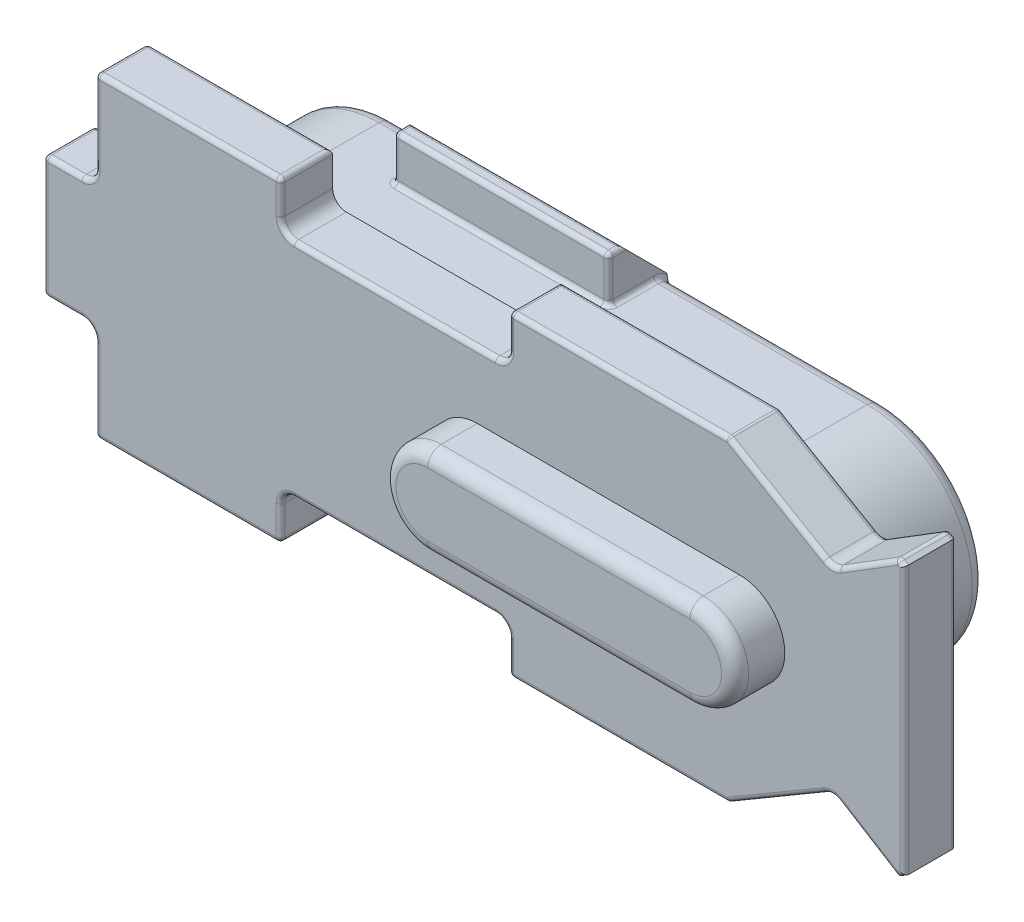
SolidWorks part; units mm, degrees
ref_plane "Front Plane" through (0, 0, 0) normal (0, 0, 1) x (1, 0, 0)
ref_plane "Top Plane" through (0, 0, 0) normal (0, 1, 0) x (1, 0, 0)
ref_plane "Right Plane" through (0, 0, 0) normal (1, 0, 0) x (0, 0, -1)
sketch "Sketch1" plane through (0, 0, 0) normal (0, 0, 1) x (1, 0, 0)
  line L0 (0, -8.89) -> (57.15, -8.89) construction
  line L1 (0, -12.319) -> (0, -5.461)
  line L2 (0, -5.461) -> (2.921, -5.461)
  line L3 (2.921, -5.461) -> (2.921, 0)
  line L4 (2.921, 0) -> (13.335, 0)
  line L5 (13.335, 0) -> (13.335, -2.667)
  line L6 (13.335, -2.667) -> (26.162, -2.667)
  line L7 (26.162, -2.667) -> (26.162, 0)
  line L8 (26.162, 0) -> (38.481, 0)
  line L9 (38.481, 0) -> (44.323, -3.429)
  line L10 (44.323, -3.429) -> (48.006, -1.143)
  line L11 (48.006, -1.143) -> (48.3742, -1.3591)
  line L12 (48.3742, -1.3591) -> (48.3742, -16.4209)
  line L13 (48.006, -16.637) -> (48.3742, -16.4209)
  line L18 (44.323, -14.351) -> (48.006, -16.637)
  line L19 (38.481, -17.78) -> (44.323, -14.351)
  line L20 (26.162, -17.78) -> (38.481, -17.78)
  line L21 (26.162, -15.113) -> (26.162, -17.78)
  line L22 (13.335, -15.113) -> (26.162, -15.113)
  line L23 (13.335, -17.78) -> (13.335, -15.113)
  line L24 (2.921, -17.78) -> (13.335, -17.78)
  line L25 (2.921, -12.319) -> (2.921, -17.78)
  line L26 (0, -12.319) -> (2.921, -12.319)
  point P16 (48.3742, -8.89)
  dimension "D2" = 17.78
  dimension "D3" = 6.858
  dimension "D4" = 2.921
  dimension "D5" = 10.414
  dimension "D6" = 12.827
  dimension "D7" = 2.667
  dimension "D9" = 35.56
  dimension "D10" = 10.922
  dimension "D11" = 41.402
  dimension "D12" = 45.085
  dimension "D13" = 15.494
extrude "Boss-Extrude1" add sketch "Sketch1" against normal blind 2.921
sketch "Sketch2" plane through (0, 0, 0) normal (0, 0, 1) x (1, 0, 0)
  line L0 (0, -8.89) -> (57.15, -8.89) construction
  line L1 (0, -5.461) -> (0, -12.319) construction
  line L3 (39.116, -8.89) -> (24.384, -8.89) construction
  line L4 (39.116, -11.43) -> (24.384, -11.43)
  line L5 (39.116, -6.35) -> (24.384, -6.35)
  arc A0 (39.116, -11.43) -> (39.116, -6.35) centre (39.116, -8.89) ccw
  arc A1 (24.384, -6.35) -> (24.384, -11.43) centre (24.384, -8.89) ccw
  point P8 (31.75, -8.89)
  point P13 (21.844, -8.89)
  point P14 (41.656, -8.89)
  point P15 (0, 0)
  dimension "D1" = 19.812
  dimension "D2" = 5.08
  dimension "D3" = 21.844
extrude "Boss-Extrude2" add sketch "Sketch2" along normal blind 2.794
sketch "Sketch3" plane through (0, 0, -2.921) normal (0, 0, -1) x (-1, 0, 0)
  line L0 (-57.15, -8.89) -> (0, -8.89) construction
  line L2 (0, -5.461) -> (0, -12.319) construction
  line L3 (-37.7825, -8.89) -> (-10.3505, -8.89) construction
  line L4 (-37.7825, -2.9845) -> (-10.3505, -2.9845)
  line L5 (-37.7825, -14.7955) -> (-10.3505, -14.7955)
  arc A0 (-37.7825, -2.9845) -> (-37.7825, -14.7955) centre (-37.7825, -8.89) ccw
  arc A1 (-10.3505, -14.7955) -> (-10.3505, -2.9845) centre (-10.3505, -8.89) ccw
  point P8 (-24.0665, -8.89)
  point P13 (-4.445, -8.89)
  point P14 (-43.688, -8.89)
  point P15 (0, 0)
  dimension "D1" = 39.243
  dimension "D2" = 11.811
  dimension "D3" = 4.445
extrude "Boss-Extrude3" add sketch "Sketch3" along normal blind 6.35
sketch "Sketch4" plane through (0, 0, -9.271) normal (0, 0, -1) x (-1, 0, 0)
  line L0 (-43.688, -8.89) -> (-4.445, -8.89) construction
  line L1 (-10.3505, -2.9845) -> (-37.7825, -2.9845) construction
  line L2 (-25.781, -2.9845) -> (-13.716, -2.9845)
  line L3 (-25.781, -2.9845) -> (-25.781, -0.4445)
  line L4 (-25.781, -0.4445) -> (-13.716, -0.4445)
  line L5 (-13.716, -2.9845) -> (-13.716, -0.4445)
  line L7 (-19.7485, -0.4445) -> (-19.7485, -2.9845) construction
  line L11 (-26.162, 0) -> (-26.162, -2.667) construction
  line L12 (-13.335, -2.667) -> (-13.335, 0) construction
  line L13 (-19.7485, -17.3355) -> (-19.7485, -14.7955) construction
  line L14 (-13.716, -14.7955) -> (-13.716, -17.3355)
  line L15 (-25.781, -17.3355) -> (-13.716, -17.3355)
  line L16 (-25.781, -14.7955) -> (-25.781, -17.3355)
  line L17 (-25.781, -14.7955) -> (-13.716, -14.7955)
  arc A0 (-37.7825, -2.9845) -> (-37.7825, -14.7955) centre (-37.7825, -8.89) ccw construction
  arc A1 (-10.3505, -14.7955) -> (-10.3505, -2.9845) centre (-10.3505, -8.89) ccw construction
  dimension "D1" = 12.065
  dimension "D2" = 2.54
extrude "Boss-Extrude4" add sketch "Sketch4" against normal blind 3.302
sketch "Sketch5" plane through (13.716, 0, 0) normal (-1, 0, 0) x (0, 0, 1)
  line L0 (-9.271, -8.89) -> (0, -8.89) construction
  line L1 (-9.271, -2.9845) -> (-9.271, -14.7955) construction
  line L2 (0, -5.461) -> (0, -12.319) construction
  line L3 (-9.271, -2.9845) -> (-6.731, -0.4445)
  line L5 (-6.731, -0.4445) -> (-9.271, -0.4445)
  line L6 (-9.271, -0.4445) -> (-9.271, -2.9845)
  line L7 (-5.969, -0.4445) -> (-9.271, -0.4445) construction
  line L8 (-9.271, -17.3355) -> (-9.271, -14.7955)
  line L9 (-6.731, -17.3355) -> (-9.271, -17.3355)
  line L10 (-9.271, -14.7955) -> (-6.731, -17.3355)
  dimension "D1" = 45
extrude "Cut-Extrude2" cut sketch "Sketch5" against normal through all
fillet "Fillet1" radius 0.762 18 edges at (12.0333, -14.7955, -9.271) (4.445, -8.89, -9.271) (12.0332, -2.9845, -9.271) (31.7817, -2.9845, -9.271) (43.688, -8.89, -9.271) (31.7817, -14.7955, -9.271) (31.75, -11.43, 2.794) (21.844, -8.89, 2.794) (31.75, -6.35, 2.794) (41.656, -8.89, 2.794) (2.921, -5.461, -1.4605) (2.921, -12.319, -1.4605) (13.335, -15.113, -1.4605) (26.162, -15.113, -1.4605) (13.335, -2.667, -1.4605) (26.162, -2.667, -1.4605) (44.323, -3.429, -1.4605) (44.323, -14.351, -1.4605) tangent propagation no
fillet "Fillet2" radius 0.254 85 edges at (13.716, -3.2077, -9.0478) (13.716, -2.9845, -7.239) (25.781, -3.2077, -9.0478) (25.781, -14.5723, -9.0478) (13.716, -14.5723, -9.0478) (46.3599, -2.1647, -2.921) (44.3214, -3.3009, -2.921) (1.0795, -5.461, -2.921) (2.6978, -5.2378, -2.921) (1.0795, -12.319, -2.921) (2.6978, -12.5422, -2.921) (46.3599, -15.6153, -2.921) (44.3214, -14.4791, -2.921) (24.0665, -14.7955, -2.921) (43.688, -8.89, -2.921) (24.0665, -2.9845, -2.921) (19.7485, -2.9845, -5.969) (13.716, -1.7145, -5.969) (25.781, -1.7145, -5.969) (25.781, -0.4445, -6.35) (19.7485, -0.4445, -5.969) (13.716, -0.4445, -6.35) (19.7485, -0.4445, -6.731) (13.716, -17.3355, -6.35) (19.7485, -17.3355, -5.969) (25.781, -17.3355, -6.35) (19.7485, -17.3355, -6.731) (8.128, 0, 0) (13.335, -0.9525, 0) (13.5582, -2.4438, 0) (19.7485, -2.667, 0) (25.9388, -2.4438, 0) (26.162, -0.9525, 0) (32.3215, 0, 0) (41.2036, -1.5981, 0) (44.3214, -3.3009, 0) (46.3599, -2.1647, 0) (48.1901, -1.2511, 0) (46.3599, -15.6153, 0) (44.3214, -14.4791, 0) (41.2036, -16.1819, 0) (32.3215, -17.78, 0) (26.162, -16.8275, 0) (25.9388, -15.3362, 0) (19.7485, -15.113, 0) (13.5582, -15.3362, 0) (13.335, -16.8275, 0) (8.128, -17.78, 0) (2.921, -15.4305, 0) (2.6978, -12.5422, 0) (1.0795, -12.319, 0) (0, -8.89, 0) (1.0795, -5.461, 0) (2.6978, -5.2378, 0) (2.921, -2.3495, 0) (25.781, -2.9845, -7.239) (25.781, -14.7955, -7.239) (13.716, -14.7955, -7.239) (19.7485, -14.7955, -5.969) (41.2036, -1.5981, -2.921) (32.3215, 0, -2.921) (8.128, 0, -2.921) (2.921, -2.3495, -2.921) (0, -8.89, -2.921) (2.921, -15.4305, -2.921) (8.128, -17.78, -2.921) (48.1901, -1.2511, -2.921) (41.2036, -16.1819, -2.921) (32.3215, -17.78, -2.921) (26.162, -17.78, -1.4605) (13.335, -17.78, -1.4605) (4.445, -8.89, -2.921) (2.921, -17.78, -1.4605) (0, -12.319, -1.4605) (0, -5.461, -1.4605) (2.921, 0, -1.4605) (13.335, 0, -1.4605) (26.162, 0, -1.4605) (38.481, 0, -1.4605) (48.006, -1.143, -1.4605) (38.481, -17.78, -1.4605) (48.3742, -8.89, 0) (48.1901, -16.5289, 0) (48.1901, -16.5289, -2.921) (48.3742, -8.89, -2.921)
